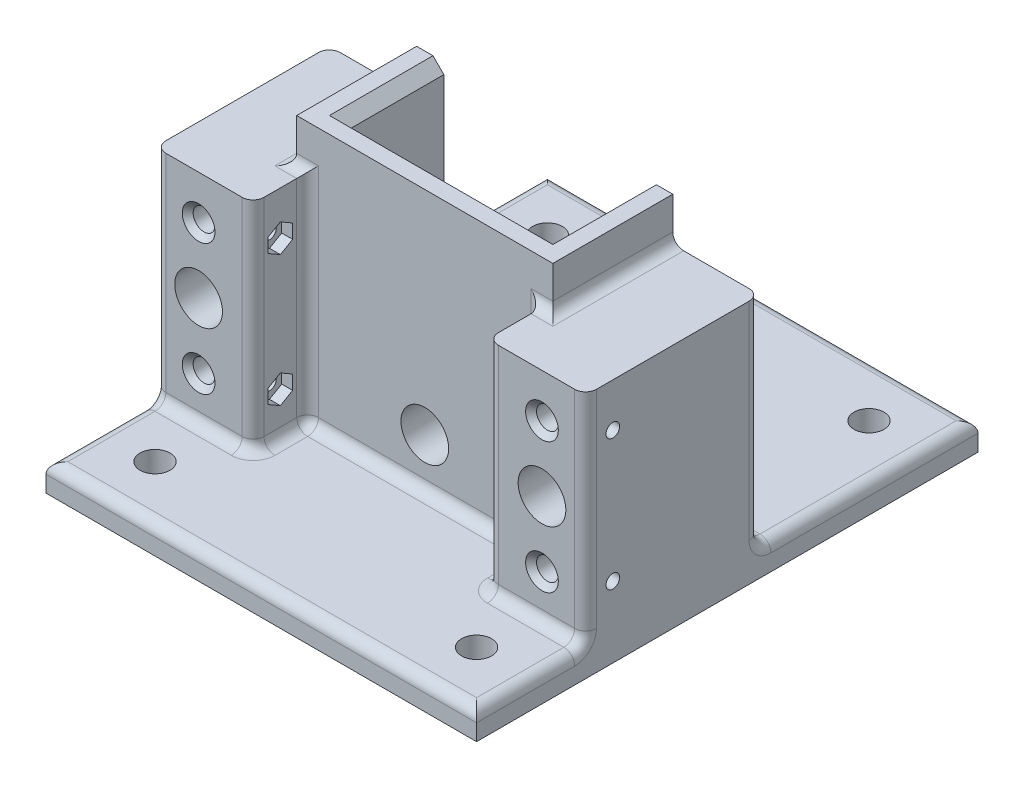
SolidWorks part; units mm, degrees
ref_plane "Спереди" through (0, 0, 0) normal (0, 0, 1) x (1, 0, 0)
ref_plane "Сверху" through (0, 0, 0) normal (0, 1, 0) x (1, 0, 0)
ref_plane "Справа" through (0, 0, 0) normal (1, 0, 0) x (0, 0, -1)
sketch "Эскиз1" plane through (0, 0, 0) normal (0, 1, 0) x (1, 0, 0)
  line L0 (0, 0) -> (0, 22)
  line L1 (0, 0) -> (47, 0)
  line L2 (23.5, 0) -> (23.5, 22) construction
  line L3 (5, 22) -> (42, 22) construction
  line L4 (0, 22) -> (5, 22)
  line L5 (5, 22) -> (5, 5)
  line L6 (5, 5) -> (42, 5)
  line L7 (42, 22) -> (42, 5)
  line L8 (47, 22) -> (42, 22)
  line L9 (47, 0) -> (47, 22)
  point P7 (23.5, 5)
  dimension "D1" = 5
  dimension "D2" = 18.5
  dimension "D3" = 17
  dimension "D4" = 5
extrude "Бобышка-Вытянуть1" add sketch "Эскиз1" along normal blind 30
sketch "Эскиз2" plane through (47, 0, 0) normal (1, 0, 0) x (0, 0, -1)
  line L0 (0, 22) -> (-10, 22)
  line L1 (0, 22) -> (0, -18)
  line L2 (-10, 22) -> (-10, -18)
  line L3 (0, -18) -> (-10, -18)
  line L4 (0, 30) -> (0, 0) construction
  line L5 (0, 30) -> (22, 30) construction
  dimension "D1" = 10
  dimension "D2" = 8
  dimension "D3" = 40
extrude "Бобышка-Вытянуть2" add sketch "Эскиз2" against normal blind 2
sketch "Эскиз3" plane through (47, 0, 0) normal (1, 0, 0) x (0, 0, -1)
  line L0 (0, 22) -> (-10, 22) construction
  line L1 (-10, 22) -> (-10, -18) construction
  line L2 (22, 22) -> (-10, 22)
  line L3 (-10, 22) -> (-10, -18)
  line L4 (-10, -18) -> (0, -18) construction
  line L5 (-10, -18) -> (22, -18)
  line L6 (22, 30) -> (22, 0) construction
  line L7 (22, 22) -> (22, -18)
extrude "Бобышка-Вытянуть3" add sketch "Эскиз3" along normal blind 16
sketch "Эскиз4" plane through (0, 0, -22) normal (0, 0, -1) x (-1, 0, 0)
  line L0 (-55, 22) -> (-55, -18) construction
  line L1 (-63, 22) -> (-47, 22) construction
  line L2 (-63, -18) -> (-47, -18) construction
  circle A0 centre (-55, 2) radius 4.375
  dimension "D1" = 8.75
extrude "Вырез-Вытянуть1" cut sketch "Эскиз4" against normal through all
sketch "Эскиз5" plane through (45, 0, 0) normal (-1, 0, 0) x (0, 0, 1)
  line L0 (5, 22) -> (5, -18) construction
  line L1 (0, 22) -> (10, 22) construction
  line L2 (10, -18) -> (0, -18) construction
  line L3 (5, 2) -> (10, 2) construction
  line L4 (10, 22) -> (10, -18) construction
  circle A0 centre (5, 14) radius 1.25
  circle A1 centre (5, -10) radius 1.25
  dimension "D1" = 12
  dimension "D2" = 2.5
extrude "Вырез-Вытянуть2" cut sketch "Эскиз5" against normal through all
sketch "Эскиз6" plane through (0, 0, -22) normal (0, 0, -1) x (-1, 0, 0)
  line L0 (-63, 15.25) -> (-63, 12.75) construction
  line L1 (-63, 15.25) -> (-63, 12.75) construction
  line L2 (-63, 14) -> (-42, 14) construction
  line L3 (-42, 30) -> (-42, 0) construction
  line L4 (-63, -8.75) -> (-63, -11.25) construction
  line L5 (-63, -8.75) -> (-63, -11.25) construction
  line L6 (-63, -10) -> (-42, -10) construction
  line L7 (-55, 14) -> (-55, -10) construction
  circle A0 centre (-55, 2) radius 4.375 construction
  circle A1 centre (-55, 2) radius 4.375 construction
  circle A2 centre (-55, 14) radius 2
  circle A3 centre (-55, -10) radius 2
  dimension "D1" = 4
  dimension "D2" = 4
extrude "Вырез-Вытянуть3" cut sketch "Эскиз6" against normal through all
sketch "Эскиз7" plane through (45, 0, 0) normal (-1, 0, 0) x (0, 0, 1)
  line L0 (5, 14) -> (5, 16.5981) construction
  line L1 (5, 11.4019) -> (7.25, 12.701)
  line L2 (7.25, 12.701) -> (7.25, 15.299)
  line L3 (7.25, 15.299) -> (5, 16.5981)
  line L4 (5, 16.5981) -> (2.75, 15.299)
  line L5 (2.75, 15.299) -> (2.75, 12.701)
  line L6 (2.75, 12.701) -> (5, 11.4019)
  line L7 (5, -7.4019) -> (2.75, -8.701)
  line L8 (2.75, -8.701) -> (2.75, -11.299)
  line L9 (2.75, -11.299) -> (5, -12.5981)
  line L10 (5, -12.5981) -> (7.25, -11.299)
  line L11 (7.25, -11.299) -> (7.25, -8.701)
  line L12 (7.25, -8.701) -> (5, -7.4019)
  line L13 (5, -10) -> (5, -7.4019) construction
  circle A0 centre (5, 14) radius 1.25 construction
  circle A1 centre (5, -10) radius 1.25 construction
  circle A2 centre (5, 14) radius 1.25 construction
  circle A3 centre (5, -10) radius 1.25 construction
  circle A4 centre (5, 14) radius 2.25 construction
  circle A5 centre (5, -10) radius 2.25 construction
  dimension "D1" = 4.5
  dimension "D2" = 4.5
extrude "Вырез-Вытянуть4" cut sketch "Эскиз7" against normal blind 2
chamfer "Фаска2" distance 3 angle 45 1 edges at (50.625, 2, -22)
chamfer "Фаска3" distance 1 angle 45 2 edges at (53, -10, -22) (53, 14, -22)
sketch "Эскиз8" plane through (0, 0, -5) normal (0, 0, -1) x (-1, 0, 0)
  line L0 (-23.5, 30) -> (-23.5, 0) construction
  line L1 (-42, 30) -> (-5, 30) construction
  line L2 (-42, 0) -> (-5, 0) construction
ref_plane "Sym" through (23.5, 0, 0) normal (1, 0, 0) x (0, -1, 0)
mirror "Зеркальное отражение2" about plane through (23.5, 0, 0) normal (1, 0, 0) of "Вырез-Вытянуть1", "Бобышка-Вытянуть3", "Бобышка-Вытянуть2", "Вырез-Вытянуть4", "Вырез-Вытянуть3", "Вырез-Вытянуть2"
chamfer "Фаска4" distance 3 angle 45 1 edges at (-3.625, 2, -22)
sketch "Эскиз9" plane through (0, 0, 0) normal (0, -1, 0) x (1, 0, 0)
  line L9 (2, 0) -> (0, 0)
  line L10 (2, 0) -> (0, 0)
  line L12 (0, -22) -> (5, -22)
  line L13 (5, -22) -> (5, -5)
  line L14 (5, -5) -> (42, -5)
  line L15 (42, -5) -> (42, -22)
  line L16 (42, -22) -> (47, -22)
  line L17 (47, -22) -> (47, 0)
  line L18 (47, 0) -> (45, 0)
  line L19 (45, 0) -> (2, 0)
  line L20 (0, 0) -> (0, -22)
  line L21 (0, 0) -> (0, -22)
  line L22 (0, -22) -> (47, -22)
  line L27 (47, -22) -> (47, 0)
  line L28 (47, 0) -> (45, 0)
  line L29 (45, 0) -> (2, 0)
  dimension "D1" = 0
extrude "Бобышка-Вытянуть4" add sketch "Эскиз9" along normal up to surface (18 mm away) up to face at (51.5, -18, -2.1667)
sketch "Эскиз10" plane through (0, 0, -22) normal (0, 0, -1) x (-1, 0, 0)
  line L0 (-23.5, 0) -> (-23.5, -18) construction
  line L1 (-5, 0) -> (-42, 0) construction
  line L2 (-63, -18) -> (16, -18) construction
  circle A0 centre (-23.5, -9) radius 4.375
  circle A1 centre (8, 2) radius 4.375 construction
extrude "Вырез-Вытянуть5" cut sketch "Эскиз10" against normal through all
chamfer "Фаска6" distance 3 angle 45 1 edges at (19.125, -9, -22)
sketch "Эскиз11" plane through (0, 0, 10) normal (0, 0, 1) x (1, 0, 0)
  line L0 (55, 16) -> (55, -12) construction
  circle A0 centre (55, 14) radius 2 construction
  circle A1 centre (55, -10) radius 2 construction
ref_plane "Плоскость1" through (55, 0, 0) normal (-1, 0, 0) x (0, -1, 0)
chamfer "Фаска7" distance 1 angle 45 4 edges at (-6, -10, 10) (-6, 14, 10) (53, -10, 10) (53, 14, 10)
chamfer "Фаска8" distance 2 angle 45 1 edges at (5, 30, -13.5)
fillet "Скругление3" radius 2 6 edges at (45, 2, 0) (2, 2, 0)
sketch "Эскиз12" plane through (0, -18, 0) normal (0, -1, 0) x (1, 0, 0)
  line L0 (-16, 10) -> (63, 10)
  line L1 (-16, 10) -> (-16, -62)
  line L2 (63, 10) -> (63, -62)
  line L3 (-16, -62) -> (63, -62)
  line L4 (-16, 10) -> (-16, -22) construction
  line L5 (63, 10) -> (63, -22) construction
  line L6 (63, -22) -> (-16, -22) construction
  line L8 (45, 10) -> (63, 10) construction
  dimension "D1" = 40
extrude "Бобышка-Вытянуть5" add sketch "Эскиз12" along normal blind 5
fillet "Скругление7" radius 2 1 edges
sketch "Эскиз13" plane through (0, 0, 10) normal (0, 0, 1) x (1, 0, 0)
  line L0 (-16, 22) -> (-16, -23) construction
  line L1 (63, -23) -> (-16, -23) construction
  line L2 (63, 22) -> (63, -23) construction
  line L3 (45, -18) -> (2, -18) construction
  line L4 (-16, -18) -> (-16, -23)
  line L5 (63, -23) -> (-16, -23)
  line L6 (63, -18) -> (63, -23)
  line L7 (63, -18) -> (-16, -18)
extrude "Бобышка-Вытянуть6" add sketch "Эскиз13" along normal blind 20
fillet "Скругление10" radius 2 14 edges at (2.5858, -18, 0.5858) (23.5, -18, 0) (44.4142, -18, 0.5858) (23.5, -18, 30)
fillet "Скругление11" radius 2 7 edges at (63, -17.4142, -22.5858) (-16, -17.4142, -22.5858) (23.5, -18, -62)
sketch "Эскиз14" plane through (0, -18, 0) normal (0, 1, 0) x (1, 0, 0)
  line L0 (-14, -20) -> (61, -20) construction
  line L1 (-14, -12) -> (-14, -28) construction
  line L2 (61, -28) -> (61, -12) construction
  line L3 (-14, 52) -> (61, 52) construction
  line L4 (-14, 60) -> (-14, 24) construction
  line L5 (61, 24) -> (61, 60) construction
  line L6 (63, -30) -> (-16, -30) construction
  line L8 (-16, 62) -> (63, 62) construction
  line L9 (-6, -20) -> (-6, 52) construction
  line L10 (23.5, -20) -> (23.5, 52) construction
  line L11 (-16, -30) -> (-16, -12) construction
  circle A0 centre (-6, -20) radius 2.75
  circle A1 centre (53, -20) radius 2.75
  circle A2 centre (-6, 52) radius 2.75
  circle A3 centre (53, 52) radius 2.75
  dimension "D3" = 5.5
  dimension "D1" = 10
  dimension "D2" = 10
  dimension "D4" = 10
extrude "Вырез-Вытянуть6" cut sketch "Эскиз14" against normal through all
chamfer "Фаска9" distance 1 angle 45 2 edges at (-6, -10, -22) (-6, 14, -22)
chamfer "Фаска10" distance 2 angle 45 2 edges at (42, 30, -13.5) (22.5, 30, -5)
